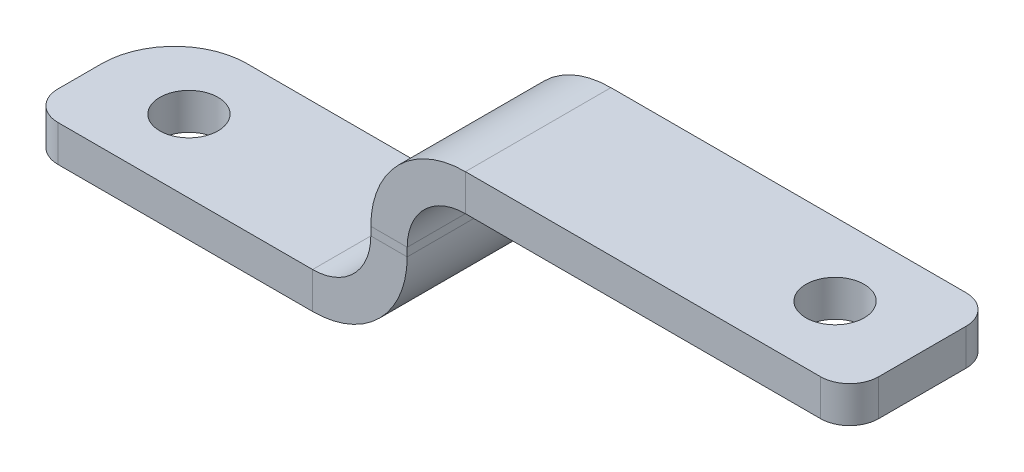
SolidWorks part; units mm, degrees
note: The reader was unsure of these and kept them because the rebuilt part matched: flange length of "Edge-Flange1", "Edge-Flange2".
ref_plane "Front Plane" through (0, 0, 0) normal (0, 0, 1) x (1, 0, 0)
ref_plane "Top Plane" through (0, 0, 0) normal (0, 1, 0) x (1, 0, 0)
ref_plane "Right Plane" through (0, 0, 0) normal (1, 0, 0) x (0, 0, -1)
sketch "Sketch1" plane through (0, 0, 0) normal (0, 1, 0) x (1, 0, 0)
  line L0 (4, 10) -> (0, 10)
  line L1 (4, 10) -> (47, 10)
  line L2 (0, 6) -> (0, -6)
  line L3 (4, -10) -> (47, -10)
  line L4 (47, 10) -> (47, -10)
  line L5 (0, 10) -> (0, 6)
  line L6 (4, -10) -> (0, -10)
  line L7 (0, -10) -> (0, -6)
  circle A0 centre (12, 0) radius 4
  point P4 (0, 0)
  dimension "D4" = 8
  dimension "D5" = 4
  dimension "D1" = 20
  dimension "D2" = 12
  dimension "D3" = 10
  dimension "D6" = 35
  dimension "D7" = 4
  dimension "D8" = 4
  dimension "D9" = 4
base flange "Base-Flange1" sketch "Sketch1" thickness 5 reverse thickness direction yes parameters "D1"=0.7366
edge flange "Edge-Flange1" sketch "Sketch8" flange angle 90 flange length 22.15 flange position material outside bend radius 8 thickness 5 relief rectangular parameters "D6"=10
sketch "Sketch8" plane through (47, 5, 0) normal (1, 0, 0) x (0, 0, -1)
  line L2 (-10, 0) -> (-10, 17.15)
  line L3 (-10, 17.15) -> (10, 17.15)
  line L4 (10, 17.15) -> (10, 0)
  line L5 (-10, 0) -> (10, 0) construction
  line L6 (-10, 0) -> (10, 0)
bend "EdgeBend1" bend radius 8 bend angle 90 parameters "D5"=1
edge flange "Edge-Flange2" sketch "Sketch13" flange angle 90 flange length 65.81 flange position material outside bend radius 8 thickness 5 relief rectangular parameters "D6"=10
sketch "Sketch13" plane through (52, 22.15, 0) normal (0, 1, 0) x (0, 0, 1)
  line L2 (-10, 0) -> (-10, 60.81)
  line L3 (-10, 60.81) -> (10, 60.81)
  line L4 (10, 60.81) -> (10, 0)
  line L7 (-10, 0) -> (10, 0) construction
  line L8 (-10, 0) -> (10, 0)
bend "EdgeBend2" bend radius 8 bend angle 90 parameters "D5"=2
sketch "Sketch14" plane through (0, 27.15, 0) normal (0, 1, 0) x (1, 0, 0)
  line L0 (60, -10) -> (112.81, -10) construction
  line L1 (112.81, -10) -> (112.81, 10) construction
  circle A0 centre (100.81, 0) radius 4
  dimension "D1" = 8
  dimension "D2" = 10
  dimension "D3" = 12
extrude "Cut-Extrude1" cut sketch "Sketch14" against normal blind 10 normal cut yes
fillet "Fillet1" radius 4 2 edges at (112.81, 24.65, -10) (112.81, 24.65, 10)
fillet "Fillet3" radius 4 1 edges at (0, 2.5, 10)
fillet "Fillet4" radius 10 1 edges at (0, 2.5, -10)
sketch "Bend-Lines1" [suppressed] plane through (0, 0, 0) normal (0, 1, 0) x (1, 0, 0)
sketch "Bounding-Box1" [suppressed] plane through (0, 0, 0) normal (0, 1, 0) x (1, 0, 0)
sheet metal parameters "Sheet-Metal1" thickness 5 parameters "D1"=0.7366
flat pattern "Flat-Pattern1" [suppressed]
sketch "Bend-Lines2" plane through (0, 0, 0) normal (0, 1, 0) x (1, 0, 0)
sketch3d "Bounding-Box2" [suppressed]
  line L0 (-4, -4, 0) -> (43, -4, 0) construction
  line L1 (-4, 16, 0) -> (43, 16, 0) construction
  line L2 (-4, -4, 0) -> (-4, 16, 0) construction
  line L3 (43, -4, 0) -> (43, 16, 0) construction
sheet metal parameters "Sheet-Metal2" thickness 5 parameters "D1"=0.7366
flat pattern "Flat-Pattern1"
sketch "Bend-Lines2" plane through (0, 0, 0) normal (0, -1, 0) x (-1, 0, 0)
  line L0 (-48.1051, 10) -> (-48.1051, -10) construction
  line L1 (-48.1051, 10) -> (-48.1051, -10) construction
sketch3d "Bounding-Box2" [suppressed]
  line L0 (4, -4, 0) -> (-62.3602, -4, 0) construction
  line L1 (4, 16, 0) -> (-62.3602, 16, 0) construction
  line L2 (4, -4, 0) -> (4, 16, 0) construction
  line L3 (-62.3602, -4, 0) -> (-62.3602, 16, 0) construction
bend of the flat pattern "Flatten-<EdgeBend1>1"
sheet metal parameters "Sheet-Metal3" thickness 5 parameters "D1"=0.7366
flat pattern "Flat-Pattern1"
sketch "Bend-Lines2" plane through (0, 0, 0) normal (0, -1, 0) x (-1, 0, 0)
  line L0 (-48.1051, 10) -> (-48.1051, -10) construction
  line L1 (-48.1051, 10) -> (-48.1051, -10) construction
  line L2 (-67.4653, 10) -> (-67.4653, -10) construction
  line L3 (-67.4653, 10) -> (-67.4653, -10) construction
sketch3d "Bounding-Box2" [suppressed]
  line L0 (4, -3.9999, 0) -> (-125.3804, -4, 0) construction
  line L1 (4, 16, 0) -> (-125.3804, 15.9999, 0) construction
  line L2 (4, -3.9999, 0) -> (4, 16, 0) construction
  line L3 (-125.3804, -4, 0) -> (-125.3804, 15.9999, 0) construction
bend of the flat pattern "Flatten-<EdgeBend1>1"
bend of the flat pattern "Flatten-<EdgeBend2>1"
sheet metal parameters "Sheet-Metal4" thickness 5 parameters "D1"=0.7366
flat pattern "Flat-Pattern1"
sketch "Bend-Lines2" plane through (0, 0, 0) normal (0, -1, 0) x (-1, 0, 0)
  line L0 (-47.2467, 10) -> (-47.2467, -10) construction
  line L1 (-47.2467, 10) -> (-47.2467, -10) construction
  line L2 (-64.89, 10) -> (-64.89, -10) construction
  line L3 (-64.89, 10) -> (-64.89, -10) construction
sketch3d "Bounding-Box2" [suppressed]
  line L0 (0, -10, 0) -> (-125.9467, -10, 0) construction
  line L1 (0, 10, 0) -> (-125.9467, 10, 0) construction
  line L2 (0, -10, 0) -> (0, 10, 0) construction
  line L3 (-125.9467, -10, 0) -> (-125.9467, 10, 0) construction
bend of the flat pattern "Flatten-<EdgeBend1>1"
bend of the flat pattern "Flatten-<EdgeBend2>1"
